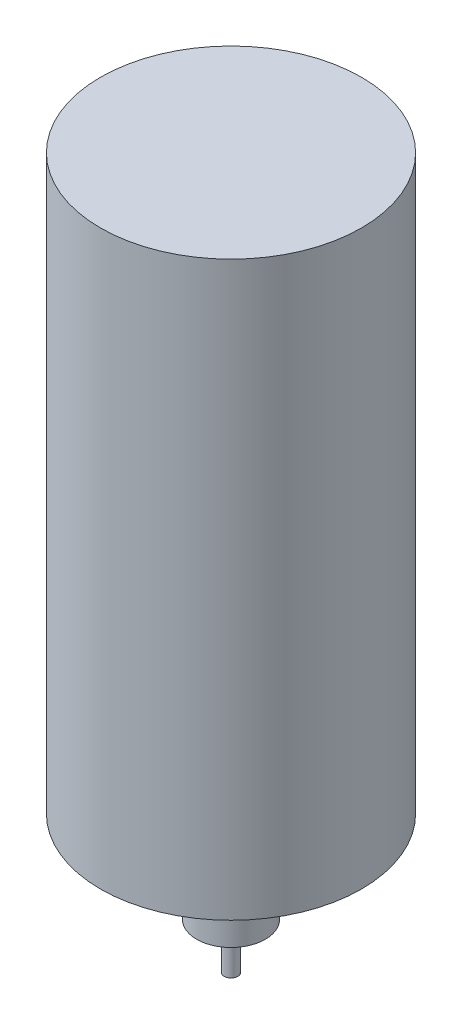
SolidWorks part; units mm, degrees
ref_plane "Front Plane" through (0, 0, 0) normal (0, 0, 1) x (1, 0, 0)
ref_plane "Top Plane" through (0, 0, 0) normal (0, 1, 0) x (1, 0, 0)
ref_plane "Right Plane" through (0, 0, 0) normal (1, 0, 0) x (0, 0, -1)
sketch "Sketch1" plane through (0, 0, 0) normal (0, 1, 0) x (1, 0, 0)
  circle A0 centre (0, 0) radius 28.5
  dimension "D1" = 57
extrude "Boss-Extrude1" add sketch "Sketch1" along normal mid plane 125
sketch "Sketch2" plane through (0, -62.5, 0) normal (0, -1, 0) x (1, 0, 0)
  circle A0 centre (0, 0) radius 7.5
  dimension "D1" = 15
extrude "Boss-Extrude2" add sketch "Sketch2" along normal blind 20
sketch "Sketch3" plane through (0, -82.5, 0) normal (0, -1, 0) x (1, 0, 0)
  circle A0 centre (0, 0) radius 1.5
  dimension "D1" = 3
extrude "Boss-Extrude3" add sketch "Sketch3" along normal blind 10
